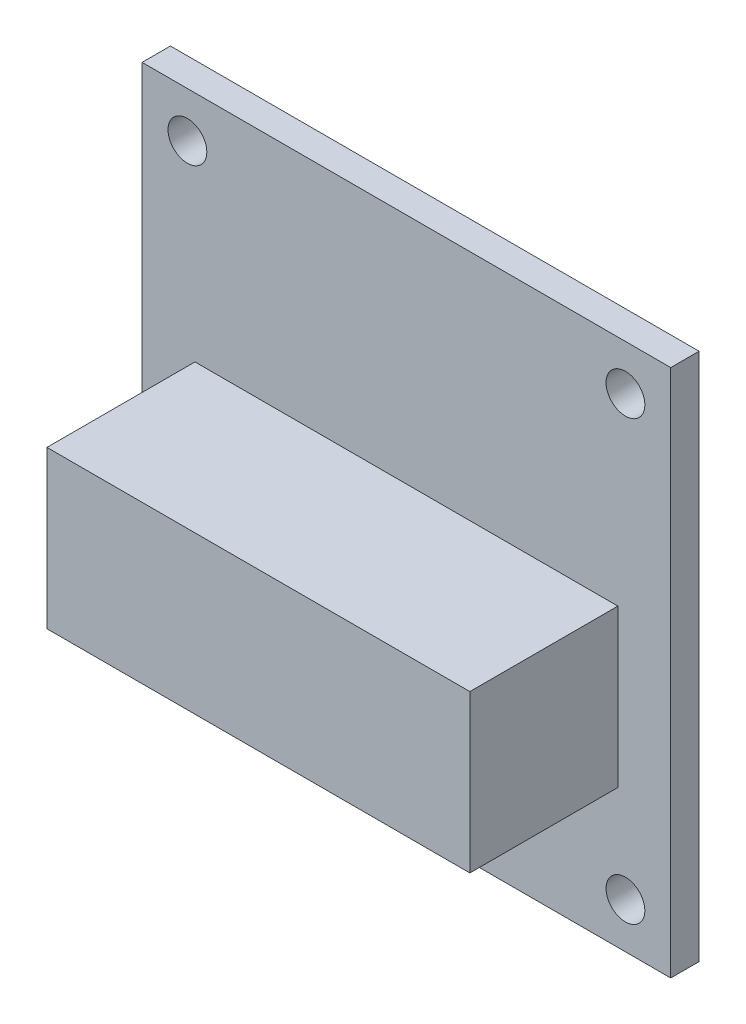
SolidWorks part; units mm, degrees
ref_plane "Front Plane" through (0, 0, 0) normal (0, 0, 1) x (1, 0, 0)
ref_plane "Top Plane" through (0, 0, 0) normal (0, 1, 0) x (1, 0, 0)
ref_plane "Right Plane" through (0, 0, 0) normal (1, 0, 0) x (0, 0, -1)
sketch "Sketch1" plane through (0, 0, 0) normal (0, 0, 1) x (1, 0, 0)
  line L1 (-22.225, -22.225) -> (22.225, -22.225)
  line L2 (-22.225, -22.225) -> (-22.225, 22.225)
  line L3 (-22.225, 22.225) -> (22.225, 22.225)
  line L4 (22.225, -22.225) -> (22.225, 22.225)
  line L5 (-22.225, -22.225) -> (22.225, 22.225) construction
  line L6 (-22.225, 22.225) -> (22.225, -22.225) construction
  point P0 (0, 0)
  dimension "D1" = 44.45
  dimension "D2" = 44.45
extrude "Boss-Extrude1" add sketch "Sketch1" along normal blind 2.3813
sketch "Sketch4" plane through (0, 0, 2.3813) normal (0, 0, 1) x (1, 0, 0)
  line L0 (-18.415, 22.225) -> (-18.415, 18.415) construction
  line L1 (22.225, 22.225) -> (-22.225, 22.225) construction
  line L2 (-18.415, 18.415) -> (-22.225, 18.415) construction
  line L3 (-22.225, 22.225) -> (-22.225, -22.225) construction
  dimension "D1" = 3.81
hole_wizard "#4 Clearance Hole1" positions "Sketch6" profile "Sketch5" hole size "#4" standard "ANSI Inch"
sketch "Sketch6" plane through (0, 0, 2.3813) normal (0, 0, 1) x (1, 0, 0)
  point P0 (-18.415, 18.415)
sketch "Sketch5" plane through (-18.415, 18.415, 2.3813) normal (1, 0, 0) x (0, -1, 0)
  line L0 (0, 0) -> (0, 4.1556)
  line L1 (0, 4.1556) -> (1.6319, 3.175)
  line L2 (1.6319, 3.175) -> (1.6319, 0)
  line L5 (1.6319, 0) -> (0, 0)
  line L10 (0, 4.1556) -> (-1.632, 3.175) construction
  line L11 (0, -6.35) -> (0, 107.95) construction
  dimension "Hole Dia." = 3.2639
  dimension "Hole Depth" = 3.175
  dimension "Drill Angle" = 118
mirror "Mirror1" about plane through (0, 0, 0) normal (1, 0, 0) of "#4 Clearance Hole1"
mirror "Mirror2" about plane through (0, 0, 0) normal (0, 1, 0) of "Mirror1"
sketch "Sketch2" plane through (0, 0, 2.3813) normal (0, 0, 1) x (1, 0, 0)
  line L1 (-17.78, -10.5745) -> (17.78, -10.5745)
  line L2 (-17.78, -10.5745) -> (-17.78, 2.6335)
  line L3 (-17.78, 2.6335) -> (17.78, 2.6335)
  line L4 (17.78, -10.5745) -> (17.78, 2.6335)
  line L5 (-17.78, -10.5745) -> (17.78, 2.6335) construction
  line L6 (-17.78, 2.6335) -> (17.78, -10.5745) construction
  point P0 (0, -3.9705)
  dimension "D1" = 35.56
  dimension "D2" = 13.208
extrude "Boss-Extrude2" add sketch "Sketch2" along normal blind 12.446
